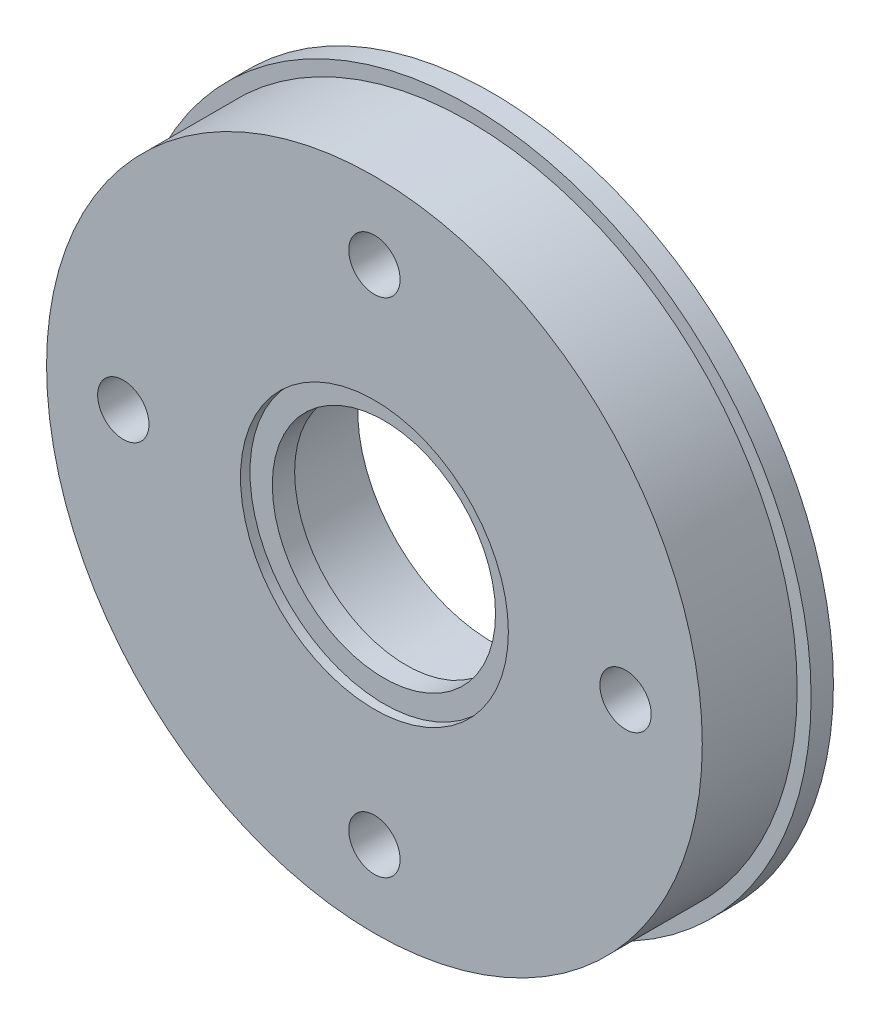
SolidWorks part; units mm, degrees
ref_plane "Front Plane" through (0, 0, 0) normal (0, 0, 1) x (1, 0, 0)
ref_plane "Top Plane" through (0, 0, 0) normal (0, 1, 0) x (1, 0, 0)
ref_plane "Right Plane" through (0, 0, 0) normal (1, 0, 0) x (0, 0, -1)
sketch "Sketch1" plane through (0, 0, 0) normal (0, 0, 1) x (1, 0, 0)
  circle A0 centre (0, 0) radius 29.375
  circle A1 centre (0, 0) radius 12
  circle A2 centre (0, 0) radius 10
  circle A3 centre (0, 0) radius 30.625
  dimension "D1" = 58.75
  dimension "D2" = 24
  dimension "D3" = 20
  dimension "D4" = 61.25
extrude "Boss-Extrude1" add sketch "Sketch1" along normal blind 2 contours A3 A0 | A0 A1 region at (-28.5441, 0, 0) region at (-29.7588, 0, 0)
extrude "Boss-Extrude2" add sketch "Sketch1<3>" along normal blind 8.5 from surface contours A0 A1 region at (-28.5441, 0, 0) starting at face at (30.625, 0, 2)
sketch "Sketch1<3>" plane through (0, 0, 0) normal (0, 0, 1) x (1, 0, 0) same geometry as "Sketch1"
extrude "Boss-Extrude3" add sketch "Sketch1<4>" along normal blind 2 from offset 7.65 contours A1 A2 region at (-11.6606, 0, 0)
sketch "Sketch1<4>" plane through (0, 0, 0) normal (0, 0, 1) x (1, 0, 0) same geometry as "Sketch1"
sketch "Sketch2" plane through (0, 0, 10.5) normal (0, 0, 1) x (1, 0, 0)
  circle A0 centre (0, 0) radius 22.5 construction
  circle A1 centre (0, 22.5) radius 2.3
  circle A2 centre (22.5, 0) radius 2.3
  circle A3 centre (0, -22.5) radius 2.3
  circle A4 centre (-22.5, 0) radius 2.3
  point P5 (-25.6827, -1.3463)
  point P6 (0, 0)
  point P14 (0, 0)
  dimension "D1" = 45
  dimension "D2" = 4.6
  dimension "D3" = 4
extrude "Cut-Extrude1" cut sketch "Sketch2" against normal blind 9
